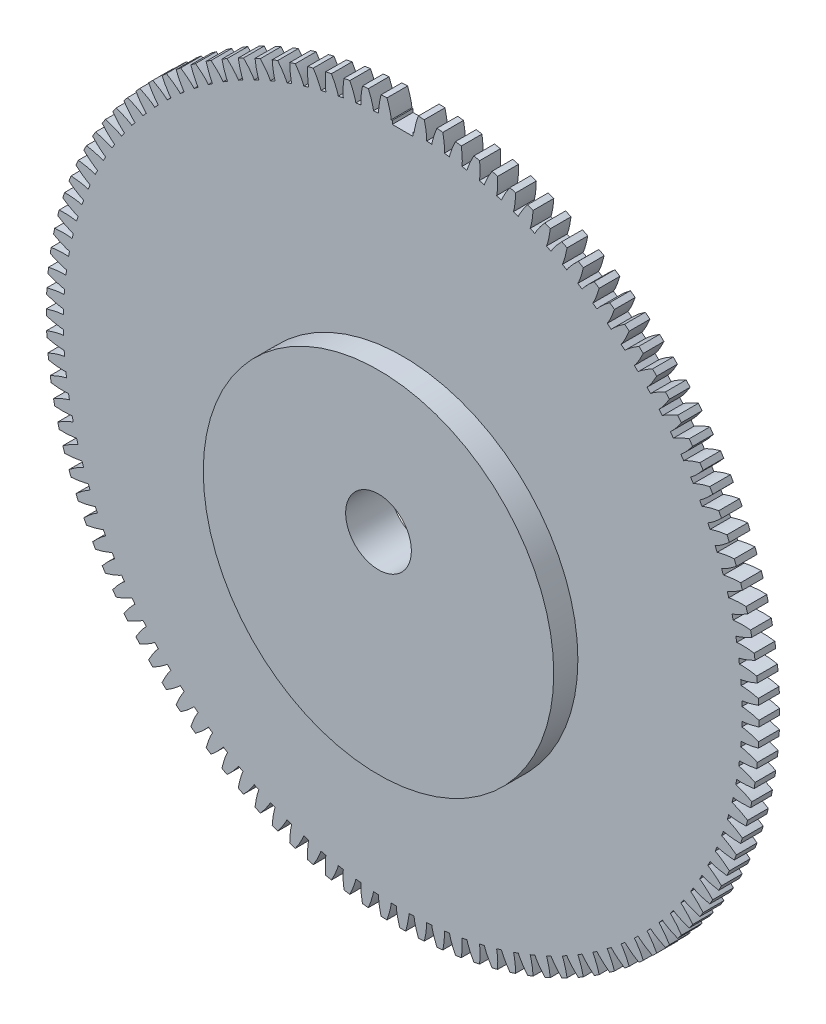
SolidWorks part; units mm, degrees
material "Brass"
ref_plane "Front Plane" through (0, 0, 0) normal (0, 0, 1) x (1, 0, 0)
ref_plane "Top Plane" through (0, 0, 0) normal (0, 1, 0) x (1, 0, 0)
ref_plane "Right Plane" through (0, 0, 0) normal (1, 0, 0) x (0, 0, -1)
sketch "Sketch1" plane through (0, 0, 0) normal (0, 0, 1) x (1, 0, 0)
  circle A0 centre (0, 0) radius 51.6467
  dimension "D1" = 103.2933
extrude "Boss-Extrude1" add sketch "Sketch1" along normal blind 3
sketch "Sketch2" plane through (0, 0, 0) normal (0, 0, 1) x (1, 0, 0)
  spline S0 degree 4 poles (49.1734, 0.9164) (49.1838, 0.9166) (49.2037, 0.9164) (49.236, 0.9157) (49.2811, 0.9138) (49.3345, 0.9109) (49.3975, 0.9065) (49.4669, 0.9007) (49.5426, 0.8933) (49.6181, 0.8849) (49.6937, 0.8757) (49.769, 0.8656) (49.8604, 0.8525) (49.9703, 0.8355) (50.099, 0.8136) (50.2454, 0.7864) (50.3952, 0.7562) (50.5429, 0.7245) (50.6927, 0.69) (50.8381, 0.655) (50.9896, 0.6161) (51.1298, 0.579) (51.2875, 0.5348) (51.415, 0.4982) (51.584, 0.4471) (51.6841, 0.416) (51.8014, 0.3786) (51.8537, 0.3614) (51.8859, 0.3509) knots 0 0 0 0 0 0.015084 0.028532 0.04661 0.064855 0.092111 0.119476 0.146842 0.174209 0.201575 0.228941 0.256307 0.307035 0.361767 0.4165 0.471232 0.525964 0.580697 0.635429 0.690161 0.744894 0.799626 0.854358 0.909091 0.954545 1 1 1 1 1 construction
  spline S1 degree 4 poles (49.1734, 0.9164) (49.1838, 0.9166) (49.2037, 0.9164) (49.236, 0.9157) (49.2811, 0.9138) (49.3345, 0.9109) (49.3975, 0.9065) (49.4669, 0.9007) (49.5426, 0.8933) (49.6181, 0.8849) (49.6937, 0.8757) (49.769, 0.8656) (49.8604, 0.8525) (49.9703, 0.8355) (50.099, 0.8136) (50.2454, 0.7864) (50.3952, 0.7562) (50.5429, 0.7245) (50.6927, 0.69) (50.8381, 0.655) (50.9896, 0.6161) (51.1298, 0.579) (51.2875, 0.5348) (51.415, 0.4982) (51.5474, 0.4582) (51.6119, 0.4383) (51.6449, 0.428) knots 0 0 0 0 0 0.015084 0.028532 0.04661 0.064855 0.092111 0.119476 0.146842 0.174209 0.201575 0.228941 0.256307 0.307035 0.361767 0.4165 0.471232 0.525964 0.580697 0.635429 0.690161 0.744894 0.799626 0.854358 0.909091 0.909091 0.909091 0.909091 0.909091
  spline S2 degree 4 poles (49.1539, 1.6583) (49.1644, 1.6588) (49.1842, 1.66) (49.2165, 1.6624) (49.2614, 1.6666) (49.3146, 1.6723) (49.3773, 1.68) (49.4463, 1.6894) (49.5214, 1.7008) (49.5965, 1.7131) (49.6714, 1.7263) (49.7461, 1.7403) (49.8367, 1.7581) (49.9455, 1.7809) (50.0729, 1.8095) (50.2177, 1.8443) (50.3657, 1.8823) (50.5116, 1.9217) (50.6594, 1.964) (50.8027, 2.0066) (50.952, 2.0533) (51.09, 2.0977) (51.2452, 2.1502) (51.3706, 2.1933) (51.5367, 2.2532) (51.635, 2.2895) (51.7503, 2.333) (51.8016, 2.3529) (51.8332, 2.3651) knots 0 0 0 0 0 0.015084 0.028532 0.04661 0.064855 0.092111 0.119476 0.146842 0.174209 0.201575 0.228941 0.256307 0.307035 0.361767 0.4165 0.471232 0.525964 0.580697 0.635429 0.690161 0.744894 0.799626 0.854358 0.909091 0.954545 1 1 1 1 1 construction
  spline S3 degree 4 poles (49.1539, 1.6583) (49.1644, 1.6588) (49.1842, 1.66) (49.2165, 1.6624) (49.2614, 1.6666) (49.3146, 1.6723) (49.3773, 1.68) (49.4463, 1.6894) (49.5214, 1.7008) (49.5965, 1.7131) (49.6714, 1.7263) (49.7461, 1.7403) (49.8367, 1.7581) (49.9455, 1.7809) (50.0729, 1.8095) (50.2177, 1.8443) (50.3657, 1.8823) (50.5116, 1.9217) (50.6594, 1.964) (50.8027, 2.0066) (50.952, 2.0533) (51.09, 2.0977) (51.2452, 2.1502) (51.3706, 2.1933) (51.5007, 2.2403) (51.5641, 2.2634) (51.5965, 2.2754) knots 0 0 0 0 0 0.015084 0.028532 0.04661 0.064855 0.092111 0.119476 0.146842 0.174209 0.201575 0.228941 0.256307 0.307035 0.361767 0.4165 0.471232 0.525964 0.580697 0.635429 0.690161 0.744894 0.799626 0.854358 0.909091 0.909091 0.909091 0.909091 0.909091
  spline S4 degree 1 poles (49.1539, 1.6583) (49.1734, 0.9164) knots 0 0 1 1 construction
  spline S5 degree 1 poles (49.1539, 1.6583) (49.1734, 0.9164) knots 0 0 1 1
  spline S6 degree 1 poles (51.6449, 0.428) (59.9979, 0.4973) knots 0 0 1 1 construction
  spline S7 degree 1 poles (51.6449, 0.428) (59.9979, 0.4973) knots 0 0 1 1
  spline S8 degree 4 poles (59.9993, 0.2811) (59.9993, 0.2966) (59.9991, 0.3264) (59.9989, 0.3667) (59.9981, 0.4759) (59.9977, 0.5237) (59.9964, 0.6646) (59.9954, 0.7445) (59.9939, 0.8601) (59.9924, 0.9543) (59.9907, 1.0614) (59.9888, 1.1607) (59.9867, 1.2646) (59.9845, 1.3658) (59.9821, 1.4686) (59.9795, 1.5706) (59.9767, 1.6727) (59.9738, 1.7754) (59.9707, 1.8766) (59.9673, 1.9805) (59.964, 2.0797) (59.9601, 2.1868) (59.9567, 2.2809) (59.9521, 2.3964) (59.949, 2.4763) (59.9429, 2.6171) (59.9408, 2.6648) (59.9359, 2.7739) (59.934, 2.8142) (59.9326, 2.844) (59.9318, 2.8594) knots 0 0 0 0 0 0.020959 0.041918 0.083333 0.123016 0.162698 0.202381 0.242063 0.281746 0.321429 0.361111 0.400794 0.440476 0.480159 0.519841 0.559524 0.599206 0.638889 0.678571 0.718254 0.757937 0.797619 0.837302 0.876984 0.916667 0.958082 0.979041 1 1 1 1 1 construction
  spline S9 degree 4 poles (59.9979, 0.4973) (59.9978, 0.5186) (59.9974, 0.5601) (59.9964, 0.6646) (59.9954, 0.7445) (59.9939, 0.8601) (59.9924, 0.9543) (59.9907, 1.0614) (59.9888, 1.1607) (59.9867, 1.2646) (59.9845, 1.3658) (59.9821, 1.4686) (59.9795, 1.5706) (59.9767, 1.6727) (59.9738, 1.7754) (59.9707, 1.8766) (59.9673, 1.9805) (59.964, 2.0797) (59.9601, 2.1868) (59.9567, 2.2809) (59.9521, 2.3964) (59.949, 2.4763) (59.9445, 2.5807) (59.9427, 2.6222) (59.9417, 2.6435) knots 0.083333 0.083333 0.083333 0.083333 0.083333 0.123016 0.162698 0.202381 0.242063 0.281746 0.321429 0.361111 0.400794 0.440476 0.480159 0.519841 0.559524 0.599206 0.638889 0.678571 0.718254 0.757937 0.797619 0.837302 0.876984 0.916667 0.916667 0.916667 0.916667 0.916667
  spline S10 degree 1 poles (59.9417, 2.6435) (51.5965, 2.2754) knots 0 0 1 1 construction
  spline S11 degree 1 poles (59.9417, 2.6435) (51.5965, 2.2754) knots 0 0 1 1
extrude "Cut-Extrude2" cut sketch "Sketch2" against normal blind 4 and the other way blind 4
ref_axis "Axis1" through (0, 0, -0.325) along (0, 0, 1)
pattern_circular "CirPattern1" count 120 over 360 about axis through (0, 0, -0.325) along (0, 0, 1) of "Cut-Extrude2"
ref_plane "Plane1" through (0, 0, 3) normal (0, 0, 1) x (1, 0, 0)
sketch "Sketch3" plane through (0, 0, 3) normal (0, 0, 1) x (1, 0, 0)
  circle A0 centre (0, -5.08) radius 25.4
  dimension "D1" = 50.8
extrude "Boss-Extrude2" add sketch "Sketch3" along normal blind 3.5
sketch "Sketch4" plane through (0, 0, 0) normal (0, 0, 1) x (1, 0, 0)
  line L0 (-1.5, 48.6467) -> (1.5, 48.6467)
  line L1 (1.5, 48.6467) -> (1.5, 53.1467)
  line L2 (1.5, 53.1467) -> (-1.5, 53.1467)
  line L3 (-1.5, 53.1467) -> (-1.5, 48.6467)
  dimension "D1" = 3
  dimension "D2" = 4.5
extrude "Cut-Extrude4" cut sketch "Sketch4" against normal blind 4 and the other way blind 4
sketch "Sketch5" plane through (0, 0, 0) normal (0, 0, 1) x (1, 0, 0)
  circle A0 centre (0, 0) radius 4.7625
  dimension "D1" = 9.525
extrude "Cut-Extrude6" cut sketch "Sketch5" against normal blind 8.5 and the other way blind 8.5
